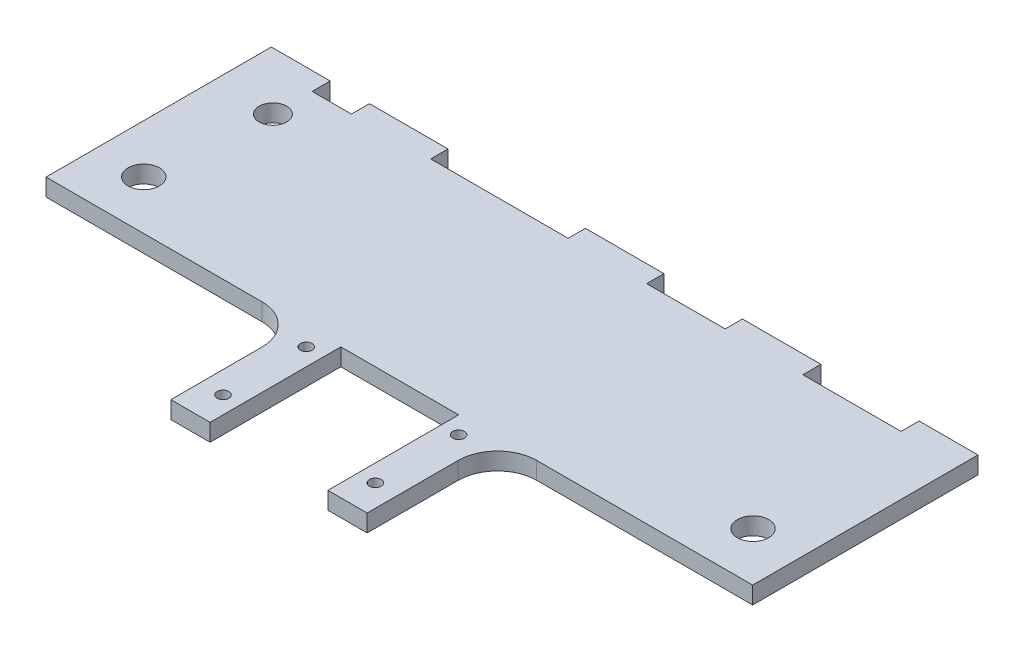
SolidWorks part; units mm, degrees
ref_plane "Front Plane" through (0, 0, 0) normal (0, 0, 1) x (1, 0, 0)
ref_plane "Top Plane" through (0, 0, 0) normal (0, 1, 0) x (1, 0, 0)
ref_plane "Right Plane" through (0, 0, 0) normal (1, 0, 0) x (0, 0, -1)
sketch "Sketch1" plane through (0, 0, 0) normal (0, 1, 0) x (1, 0, 0)
  line L0 (12.7, 67.056) -> (241.3, 67.056) construction
  line L3 (12.7, 72.898) -> (31.75, 72.898)
  line L5 (31.75, 72.898) -> (31.75, 67.056)
  line L6 (31.75, 67.056) -> (44.45, 67.056)
  line L7 (12.7, 0) -> (241.3, 0) construction
  line L8 (44.45, 67.056) -> (44.45, 72.898)
  line L10 (95.25, -42.164) -> (107.95, -42.164)
  line L12 (127, 0.1228) -> (146.05, 0.1228)
  line L13 (146.05, 0.1228) -> (146.05, -42.164)
  line L14 (127, 0.1228) -> (107.95, 0.1228)
  line L15 (107.95, 0.1228) -> (107.95, -42.164)
  line L16 (146.05, -42.164) -> (158.75, -42.164)
  line L17 (12.7, 0) -> (82.55, 0)
  line L18 (95.25, -12.7) -> (95.25, -42.164)
  line L19 (241.3, 0) -> (171.45, 0)
  line L20 (158.75, -12.7) -> (158.75, -42.164)
  line L27 (114.3, 72.898) -> (139.7, 72.898)
  line L28 (165.1, 72.898) -> (190.5, 72.898)
  line L29 (69.85, 72.898) -> (69.85, 67.31)
  line L30 (69.85, 67.31) -> (114.3, 67.31)
  line L31 (114.3, 67.31) -> (114.3, 72.898)
  line L32 (139.7, 72.898) -> (139.7, 67.31)
  line L33 (139.7, 67.31) -> (165.1, 67.31)
  line L34 (165.1, 67.31) -> (165.1, 72.898)
  line L35 (190.5, 72.898) -> (190.5, 67.056)
  line L36 (190.5, 67.056) -> (222.25, 67.056)
  line L37 (222.25, 67.056) -> (222.25, 72.898)
  line L38 (44.45, 72.898) -> (69.85, 72.898)
  line L39 (222.25, 72.898) -> (241.3, 72.898)
  line L40 (241.3, 72.898) -> (241.3, 0)
  line L41 (12.7, 72.898) -> (12.7, 0)
  arc A0 (171.45, 0) -> (158.75, -12.7) centre (171.45, -12.7) ccw
  arc A1 (95.25, -12.7) -> (82.55, 0) centre (82.55, -12.7) ccw
  point P0 (0, 0)
  point P10 (0, -41.181)
  point P27 (95.25, 0)
  dimension "D6" = 12.7
  dimension "D3" = 5.842
  dimension "D4" = 67.056
  dimension "D5" = 19.05
  dimension "D7" = 12.7
  dimension "D10" = 25.4
  dimension "D11" = 5.588
  dimension "D13" = 29.464
  dimension "D14" = 42.2868
  dimension "D15" = 12.7
  dimension "D17" = 25.4
  dimension "D20" = 228.6
extrude "Boss-Extrude1" add sketch "Sketch1" along normal blind 5.588
sketch "Sketch2" plane through (0, 0, 0) normal (0, -1, 0) x (1, 0, 0)
  point P0 (102.362, 32.3976)
  point P1 (151.638, 32.3976)
  point P3 (102.362, 5.4568)
  point P5 (151.638, 5.4568)
hole_wizard "#6 Clearance Hole1" positions "Sketch3" profile "Sketch4" hole size "#6" standard "ANSI Inch" end condition through all
sketch "Sketch3" plane through (0, 0, 0) normal (0, -1, 0) x (-1, 0, 0)
  point P0 (-102.362, -32.3976)
  point P3 (-151.638, -32.3976)
  point P6 (-151.638, -5.4568)
  point P9 (-102.362, -5.4568)
sketch "Sketch4" plane through (102.362, 0, 32.3976) normal (1, 0, 0) x (0, 0, -1)
  line L0 (0, 0) -> (0, 5.588)
  line L1 (0, 5.588) -> (1.8986, 5.588)
  line L2 (1.8986, 5.588) -> (1.8986, 0)
  line L5 (1.8986, 0) -> (0, 0)
  line L11 (0, -6.35) -> (0, 107.95) construction
  dimension "Thru Hole Dia." = 3.7973
  dimension "Thru Hole Depth" = 5.588
sketch "Sketch5" plane through (0, 5.588, 0) normal (0, 1, 0) x (1, 0, 0)
  circle A0 centre (225.552, 15.8708) radius 5.08
  circle A1 centre (28.448, 15.8708) radius 5.08
  dimension "D1" = 10.16
  dimension "D2" = 10.16
extrude "Cut-Extrude1" cut sketch "Sketch5" against normal up to next
sketch "Sketch6" plane through (0, 0, 0) normal (0, -1, 0) x (1, 0, 0)
  line L0 (12.7, -72.898) -> (12.7, 0) construction
  line L1 (44.45, -67.056) -> (31.75, -67.056) construction
  circle A0 centre (31.75, -54.356) radius 4.445
  dimension "D1" = 8.89
  dimension "D2" = 19.05
  dimension "D3" = 12.7
extrude "Cut-Extrude2" cut sketch "Sketch6" against normal up to next
